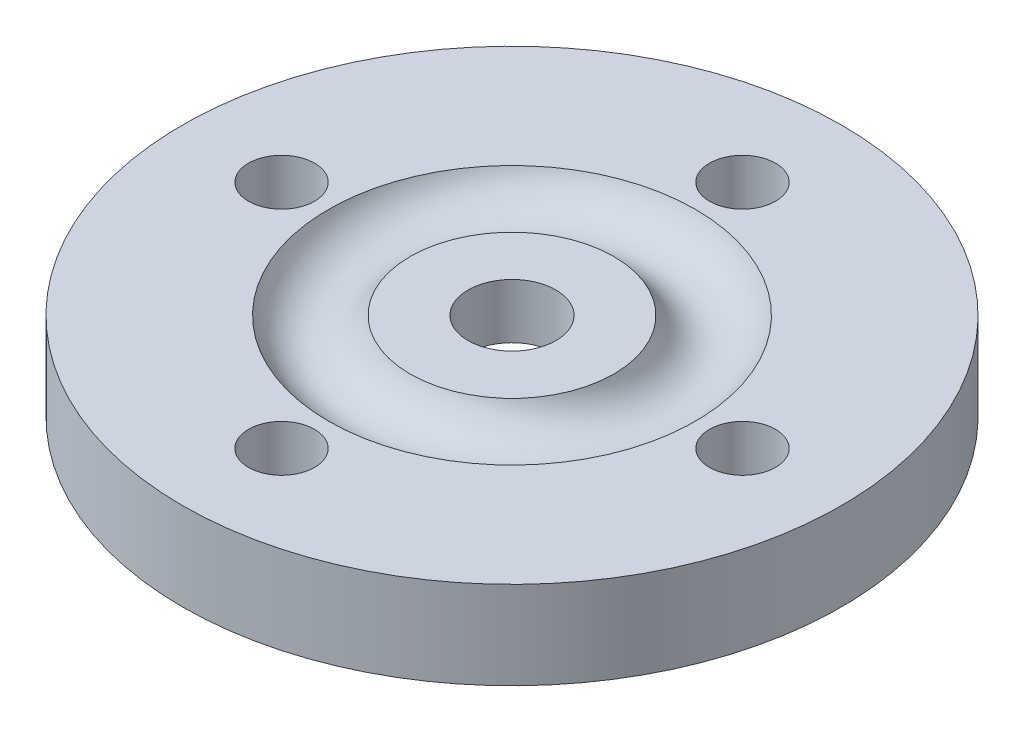
SolidWorks part; units mm, degrees
note: The reader was unsure of these and kept them because the rebuilt part matched: shared geometry of "Sketch1<3>", "Sketch1<4>".
ref_plane "Front" through (0, 0, 0) normal (0, 0, 1) x (1, 0, 0)
ref_plane "Top" through (0, 0, 0) normal (0, 1, 0) x (1, 0, 0)
ref_plane "Right" through (0, 0, 0) normal (1, 0, 0) x (0, 0, -1)
sketch "Sketch1" plane through (0, 0, 0) normal (0, 1, 0) x (1, 0, 0)
  circle A0 centre (0, 0) radius 1.5875
  circle A1 centre (0, 0) radius 3.5687
  circle A2 centre (0, 0) radius 5.1562
  circle A3 centre (0, 0) radius 6.7437
  circle A4 centre (0, 0) radius 11.9126
  circle A5 centre (0, 8.3312) radius 1.1938
  circle A6 centre (8.3312, 0) radius 1.1938
  circle A7 centre (0, -8.3312) radius 1.1938
  circle A8 centre (-8.3312, 0) radius 1.1938
sketch "Sketch3" plane through (0, 0, 0) normal (0, 0, 1) x (1, 0, 0)
  circle A1 centre (5.1562, 0.5842) radius 1.5875
extrude "Extrude1" add sketch "Sketch1" against normal blind 3.175
ref_axis "Axis1" through (0, 5.5485, 0) along (0, -1, 0)
revolve "Cut-Revolve1" cut sketch "Sketch3" angle 360 about axis through (0, 5.5485, 0) along (0, -1, 0)
extrude "Cut-Extrude1" cut sketch "Sketch1<3>" against normal blind 3.175 from offset 1.9812 contours A1 A0 | A0 offset against normal yes
sketch "Sketch1<3>" plane through (0, 0, 0) normal (0, 1, 0) x (1, 0, 0) same geometry as "Sketch1"
extrude "Cut-Extrude2" cut sketch "Sketch1<4>" against normal blind 3.175 contours A0
sketch "Sketch1<4>" plane through (0, 0, 0) normal (0, 1, 0) x (1, 0, 0) same geometry as "Sketch1"
